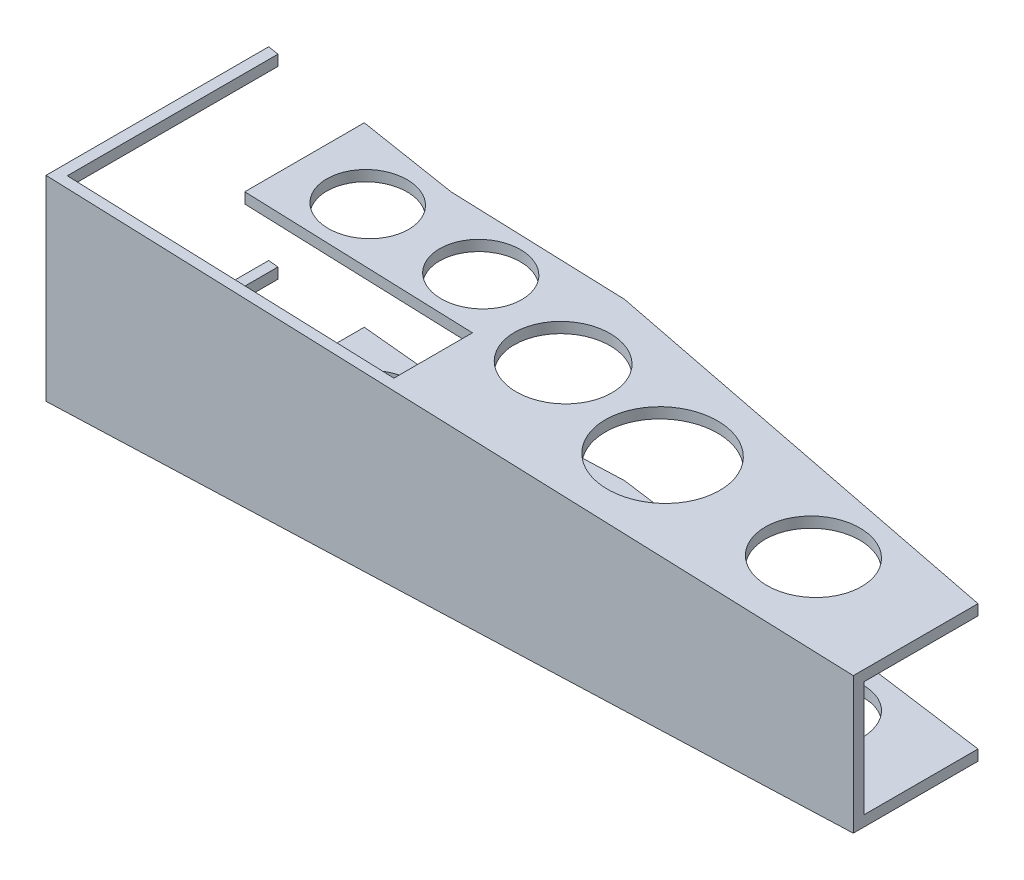
SolidWorks part; units mm, degrees
ref_plane "Front Plane" through (0, 0, 0) normal (0, 0, 1) x (1, 0, 0)
ref_plane "Top Plane" through (0, 0, 0) normal (0, 1, 0) x (1, 0, 0)
ref_plane "Right Plane" through (0, 0, 0) normal (1, 0, 0) x (0, 0, -1)
sketch "Sketch1" plane through (0, 0, 0) normal (0, 0, 1) x (1, 0, 0)
  line L0 (0, 39.555) -> (0, -39.555)
  line L1 (0, -39.555) -> (326.3, -27.585)
  line L2 (326.3, -27.585) -> (326.3, 27.585)
  line L3 (326.3, 27.585) -> (0, 39.555)
  point P4 (0, 0)
  point P6 (326.3, 0)
  dimension "D1" = 326.3
  dimension "D2" = 79.11
  dimension "D3" = 55.17
extrude "Boss-Extrude1" add sketch "Sketch1" along normal blind 105 contours L3 L0 L1 L2
sketch "Sketch3" plane through (0, 0, 0) normal (0, 1, 0) x (1, 0, 0)
  line L0 (0, -15) -> (84.7, -25.82)
  line L1 (84.7, -25.82) -> (154.7, -25.82)
  line L2 (154.7, -25.82) -> (326.3, -54.6)
  line L3 (326.3, -105) -> (326.3, 0) construction
  line L4 (326.3, -105) -> (0, -105) construction
  line L5 (0, -2.365) -> (0, 2.365) construction
  line L6 (0, -15) -> (0, 41.1139)
  line L7 (0, 41.1139) -> (326.3, 36.079)
  line L8 (326.3, 36.079) -> (326.3, -54.6)
  line L9 (0, -105) -> (0, 0) construction
  dimension "D1" = 79.18
  dimension "D2" = 84.7
  dimension "D3" = 70
  dimension "D4" = 50.4
  dimension "D5" = 90
extrude "Cut-Extrude1" cut sketch "Sketch3" against normal blind 105.1 and the other way blind 105.1
sketch "Sketch4" plane through (326.3, 0, 0) normal (1, 0, 0) x (0, 0, -1)
  line L0 (-105, -27.585) -> (-105, 27.585) construction
  line L1 (-100.7, 23.285) -> (-22.5545, 23.285)
  line L2 (-100.7, 23.285) -> (-100.7, -23.285)
  line L3 (-100.7, -23.285) -> (-22.5545, -23.285)
  line L4 (-22.5545, 23.285) -> (-22.5545, -23.285)
  line L5 (-105, 27.585) -> (-54.6, 27.585) construction
  line L6 (-105, -27.585) -> (-54.6, -27.585) construction
  dimension "D1" = 4.3
  dimension "D2" = 4.3
  dimension "D3" = 4.3
sketch "Sketch5" plane through (0, 0, 0) normal (-1, 0, 0) x (0, 0, 1)
  line L0 (105, 39.555) -> (15, 39.555) construction
  line L1 (-10.9565, 35.255) -> (100.7, 35.255)
  line L2 (-10.9565, 35.255) -> (-10.9565, -35.255)
  line L3 (-10.9565, -35.255) -> (100.7, -35.255)
  line L4 (100.7, 35.255) -> (100.7, -35.255)
  line L5 (105, 39.555) -> (105, -39.555) construction
  line L6 (105, -39.555) -> (15, -39.555) construction
  dimension "D1" = 4.3
  dimension "D2" = 4.3
  dimension "D3" = 4.3
loft "Cut-Loft1" cut profiles "Sketch4", "Sketch5" connector at (326.3, 23.285, 100.7) connector at (0, 35.255, 100.7)
sketch "Sketch6" [suppressed] plane through (0, 0, 0) normal (0, 1, 0) x (1, 0, 0)
  line L0 (326.3, -100.7) -> (0, -100.7) construction
  line L1 (-50.6225, 37.8463) -> (354.8737, 37.8463)
  line L2 (-50.6225, 37.8463) -> (-50.6225, -100.7)
  line L3 (-50.6225, -100.7) -> (354.8737, -100.7)
  line L4 (354.8737, 37.8463) -> (354.8737, -100.7)
extrude "Cut-Extrude2" [suppressed] cut sketch "Sketch6" against normal through all and the other way through all
sketch "Sketch7" [suppressed] plane through (1.2916, 35.2076, 0) normal (-0.0367, -0.9993, 0) x (0.9993, -0.0367, 0)
  line L1 (-34.6023, 151.2078) -> (362.4716, 151.2078)
  line L2 (-34.6023, 151.2078) -> (-34.6023, -20.7554)
  line L3 (-34.6023, -20.7554) -> (362.4716, -20.7554)
  line L4 (362.4716, 151.2078) -> (362.4716, -20.7554)
extrude "Cut-Extrude3" [suppressed] cut sketch "Sketch7" along normal through all
sketch "Sketch8" plane through (0, 0, 0) normal (0, 1, 0) x (1, 0, 0)
  circle A1 centre (214.6419, -70.4404) radius 23.0927
  circle A2 centre (278.3938, -73.2045) radius 19.4591
extrude "Cut-Extrude4" cut sketch "Sketch8" against normal through all both and the other way through all contours A1 | A2
sketch "Sketch9" plane through (0, 0, 0) normal (0, 1, 0) x (1, 0, 0)
  line L1 (4.3, -6.4917) -> (44.3, -6.4917)
  line L2 (4.3, -6.4917) -> (4.3, -100.7)
  line L3 (4.3, -100.7) -> (44.3, -100.7)
  line L4 (44.3, -6.4917) -> (44.3, -68.95)
  line L5 (0, -43.5105) -> (0, 43.5105) construction
  line L6 (326.3, -100.7) -> (0, -100.7) construction
  line L8 (44.3, -100.7) -> (136.3, -100.7)
  line L10 (44.3, -68.95) -> (136.3, -68.95)
  line L11 (136.3, -100.7) -> (136.3, -68.95)
  circle A0 centre (118.1107, -47.394) radius 16.6172
  circle A1 centre (72.4262, -47.394) radius 16.5207
  circle A2 centre (164.0534, -60.0412) radius 19.699
  dimension "D1" = 40
  dimension "D2" = 4.3
  dimension "D3" = 31.75
  dimension "D4" = 92
extrude "Cut-Extrude5" cut sketch "Sketch9" against normal through all both and the other way through all
equation "\"D2@Sketch4\"=\"D1@Sketch4\""
equation "\"D3@Sketch4\"=\"D1@Sketch4\""
equation "\"D2@Sketch5\"=\"D1@Sketch5\""
equation "\"D3@Sketch5\"=\"D1@Sketch5\""
